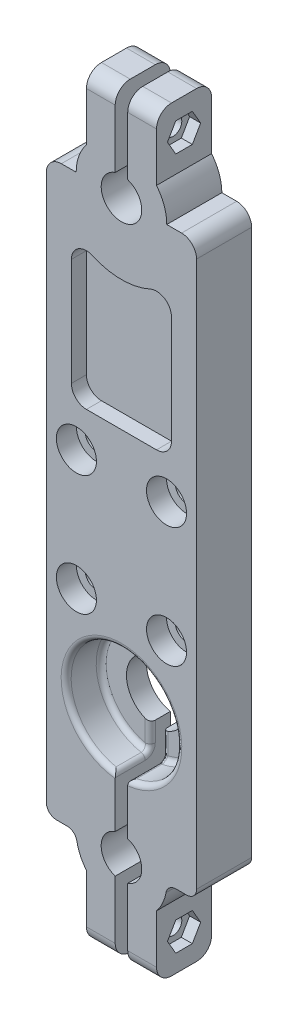
SolidWorks part; units mm, degrees
material "ABS"
ref_plane "Front Plane" through (0, 0, 0) normal (0, 0, 1) x (1, 0, 0)
ref_plane "Top Plane" through (0, 0, 0) normal (0, 1, 0) x (1, 0, 0)
ref_plane "Right Plane" through (0, 0, 0) normal (1, 0, 0) x (0, 0, -1)
sketch "Sketch2" plane through (0, 0, 0) normal (0, 0, 1) x (1, 0, 0)
  line L1 (-15, -17) -> (15, -17)
  line L2 (-15, -17) -> (-15, 17)
  line L3 (-15, 17) -> (15, 17)
  line L4 (15, -17) -> (15, 17)
  line L5 (-15, -17) -> (15, 17) construction
  line L6 (-15, 17) -> (15, -17) construction
  line L7 (-9, -12) -> (9, -12) construction
  line L8 (-9, -12) -> (-9, 12) construction
  line L9 (-9, 12) -> (9, 12) construction
  line L10 (9, -12) -> (9, 12) construction
  line L11 (-9, -12) -> (9, 12) construction
  line L12 (-9, 12) -> (9, -12) construction
  point P0 (0, 0)
  point P6 (0, 0)
  dimension "D1" = 34
  dimension "D2" = 30
  dimension "D3" = 5
  dimension "D4" = 6
extrude "Boss-Extrude1" add sketch "Sketch2" along normal blind 11 contours L3 L4 L1 L2
hole_wizard "CBORE for M4 SHCS1" positions "Sketch3" profile "Sketch4" counterbore size "M4" standard "ANSI Metric" end condition through all
sketch "Sketch3" plane through (0, 0, 11) normal (0, 0, 1) x (1, 0, 0)
  point P0 (-9, 12)
  point P3 (9, 12)
  point P6 (-9, -12)
  point P9 (9, -12)
sketch "Sketch4" plane through (-9, 12, 11) normal (1, 0, 0) x (0, -1, 0)
  line L0 (0, 0) -> (0, 11)
  line L1 (0, 11) -> (2.25, 11)
  line L3 (2.25, 11) -> (2.25, 4)
  line L4 (2.25, 4) -> (4, 4)
  line L5 (4, 4) -> (4, 0)
  line L7 (4, 0) -> (0, 0)
  line L11 (0, -6.35) -> (0, 107.95) construction
  dimension "Thru Hole Dia." = 4.5
  dimension "Thru Hole Depth" = 11
  dimension "C'Bore Dia." = 8
  dimension "C'Bore Depth" = 4
sketch "Sketch6" plane through (0, 0, 0) normal (0, 0, 1) x (1, 0, 0)
  line L0 (15, -17) -> (15, 17) construction
  line L1 (-15, -17) -> (15, -17)
  line L2 (-15, -17) -> (-15, -72.5)
  line L3 (-15, -72.5) -> (15, -72.5)
  line L4 (15, -17) -> (15, -72.5)
  line L5 (15, -17) -> (15, 17) construction
  line L6 (-15, 17) -> (15, 17)
  line L7 (-15, 17) -> (-15, 78.5)
  line L8 (-15, 78.5) -> (15, 78.5)
  line L9 (15, 17) -> (15, 78.5)
  circle A0 centre (0, -29) radius 11.05
  circle A1 centre (0, -54) radius 4.05
  circle A2 centre (0, -29) radius 10 construction
  circle A3 centre (0, -54) radius 4.05 construction
  circle A4 centre (0, 60) radius 4.05
  dimension "D1" = 22.1
  dimension "D3" = 8.1
  dimension "D5" = 18.5
  dimension "D2" = 60
  dimension "D4" = 55.5
extrude "Boss-Extrude2" add sketch "Sketch6" along normal up to surface (11 mm away) up to face at (-5, 12, 11)
sketch "Sketch8" plane through (0, 0, 0) normal (0, 0, 1) x (1, 0, 0)
  circle A0 centre (0, -29) radius 6
  circle A1 centre (0, -29) radius 11.05
  circle A2 centre (0, -29) radius 11.05 construction
  dimension "D1" = 12
extrude "Boss-Extrude3" add sketch "Sketch8" along normal blind 4 from surface starting at face at (-6.75, 12, 0)
sketch "Sketch7" plane through (0, 0, 11) normal (0, 0, 1) x (1, 0, 0)
  line L0 (-1.25, -72.5) -> (-1.25, 78.5)
  line L5 (-7, -59.7361) -> (-7, -72.5)
  line L6 (-1.25, -72.5) -> (1.25, -72.5)
  line L7 (7, -59.7361) -> (7, -72.5)
  line L8 (-1.25, 78.5) -> (1.25, 78.5)
  line L9 (-15, 78.5) -> (-15, -72.5)
  line L10 (-15, -72.5) -> (15, -72.5)
  line L11 (15, -72.5) -> (15, 78.5)
  line L12 (15, 78.5) -> (-15, 78.5)
  line L13 (-15, 78.5) -> (-15, -72.5)
  line L15 (15, -72.5) -> (15, 78.5)
  line L17 (-9.05, -54) -> (-15, -54)
  line L18 (9.05, -54) -> (15, -54)
  line L19 (1.25, -72.5) -> (1.25, 78.5)
  line L20 (-1.25, -72.5) -> (1.25, 78.5) construction
  line L21 (-7, -59.7361) -> (7, -59.7361) construction
  line L22 (-1.25, 78.5) -> (1.25, -72.5) construction
  line L26 (-15, -72.5) -> (15, -72.5)
  line L31 (-15, 60) -> (-9.05, 60)
  line L32 (9.05, 60) -> (15, 60)
  line L33 (-7, 78.5) -> (-7, 65.7361)
  line L34 (7, 78.5) -> (7, 65.7361)
  line L35 (15, 78.5) -> (-15, 78.5)
  circle A0 centre (0, -29) radius 11.05 construction
  circle A1 centre (0, -29) radius 11.05
  circle A4 centre (0, -54) radius 9.05
  circle A5 centre (0, -54) radius 9.05
  circle A8 centre (0, 60) radius 9.05
  point P1 (0, 3)
  line M9 (-15, 78.5) -> (-15, -72.5)
  line M10 (-15, -72.5) -> (15, -72.5)
  line M11 (15, -72.5) -> (15, 78.5)
  circle M13 centre (0, -54) radius 4.05
  circle M14 centre (0, -29) radius 11.05
  line M52 (15, 78.5) -> (-15, 78.5)
  circle M53 centre (0, 60) radius 4.05
  dimension "D3" = 14
  dimension "D4" = 2.5
  dimension "D1" = 0
  dimension "D2" = 5
extrude "Cut-Extrude1" cut sketch "Sketch7" against normal through all and the other way through all contours A5 L17 L13 L5 M10 | A5 L7 L18 M10 M11 | A5 L0 L19 M10 | L19 A5 L0 M13 | A5 L19 L0 M14 | L19 L0 M14 | L0 A5 L19 M13 | A8 L33 L31 M52 M9 | A8 L19 L0 M52 | A8 L32 L34 M11 M52 | L19 A8 L0 M53 region at (0, -67.7605, 11) region at (0, -60.5027, 11) region at (-11.1821, -63.6555, 11) region at (11.1821, -63.6555, 11) region at (0, -47.4973, 11) region at (0, -42.5026, 11) region at (-11.1821, 69.6555, 11) region at (0, -29, 11) region at (11.1821, 69.6555, 11) region at (0, 73.7605, 11) region at (0, 66.5027, 11)
fillet "Fillet2" radius 2 4 edges at (15, -54, 5.5) (-15, -54, 5.5) (-9.05, -54, 5.5) (9.05, -54, 5.5)
fillet "Fillet3" radius 1 12 edges at (0, -17.95, 0) (-1.25, -18.0209, 2) (-11.05, -29, 4) (-1.25, -39.9791, 7.5) (0, -17.95, 11) (1.25, -39.9791, 7.5) (11.05, -29, 4) (1.25, -18.0209, 2) (1.25, -37.4237, 4) (1.25, -20.5763, 0) (-1.25, -20.5763, 0) (-1.25, -37.4237, 4)
sketch "Sketch9" plane through (7, 0, 0) normal (1, 0, 0) x (0, 0, -1)
  line L0 (-11, -59.7361) -> (-11, -72.5) construction
  line L1 (-11, -72.5) -> (-11, -59.7361) construction
  line L2 (0, -72.5) -> (-11, -72.5) construction
  line L4 (-2.186, -66.118) -> (-3.843, -63.248)
  line L5 (-3.843, -63.248) -> (-7.157, -63.248)
  line L6 (-7.157, -63.248) -> (-8.814, -66.118)
  line L7 (-8.814, -66.118) -> (-7.157, -68.988)
  line L8 (-7.157, -68.988) -> (-3.843, -68.988)
  line L9 (-3.843, -68.988) -> (-2.186, -66.118)
  circle A0 centre (-5.5, -66.118) radius 1.75
  circle A1 centre (-5.5, -66.118) radius 2.87 construction
  point P7 (-11, -66.118)
  point P11 (-5.5, -72.5)
  dimension "D1" = 3.5
  dimension "D2" = 5.74
extrude "Cut-Extrude2" cut sketch "Sketch9" against normal through all contours A0
extrude "Cut-Extrude3" cut sketch "Sketch9<3>" against normal blind 2.2
sketch "Sketch9<3>" plane through (7, 0, 0) normal (1, 0, 0) x (0, 0, -1) same geometry as "Sketch9"
ref_plane "Plane1" through (0, 3, 0) normal (0, 1, 0) x (1, 0, 0)
mirror "Mirror1" about plane through (0, 3, 0) normal (0, 1, 0) of "Cut-Extrude3", "Cut-Extrude2"
fillet "Fillet4" radius 3 10 edges at (4.125, -72.5, 0) (4.125, -72.5, 11) (-4.125, -72.5, 11) (-4.125, -72.5, 0) (-4.125, 78.5, 11) (4.125, 78.5, 11) (4.125, 78.5, 0) (-4.125, 78.5, 0) (-15, 60, 5.5) (15, 60, 5.5)
ref_plane "Plane2" through (0, 0, 5.5) normal (0, 0, -1) x (-1, 0, 0)
sketch "Sketch11" plane through (0, 0, 0) normal (0, 0, 1) x (1, 0, 0)
  line L40 (-10, 50.1307) -> (-10, 20)
  line L41 (-10, 20) -> (10, 20)
  line L42 (10, 20) -> (10, 50.1307)
  line L43 (-15, -52) -> (-15, 57) construction
  arc A2 (-4.3364, 73.3641) -> (4.3364, 73.3641) centre (0, 60) ccw
  arc A3 (-4.3364, 73.3641) -> (4.3364, 73.3641) centre (0, 60) ccw
  point P2 (0, 20)
  dimension "D2" = 5
  dimension "D3" = 20
  dimension "D1" = 10
extrude "Cut-Extrude4" cut sketch "Sketch11" along normal blind 3 contours A3 L40 L41 L42 region at (0, 33.6511, 0)
mirror "Mirror2" about plane through (0, 0, 5.5) normal (0, 0, -1) of "Cut-Extrude4"
fillet "Fillet5" radius 3 8 edges at (-10, 50.1307, 9.5) (-10, 20, 9.5) (10, 20, 9.5) (10, 50.1307, 9.5) (10, 20, 1.5) (-10, 20, 1.5) (-10, 50.1307, 1.5) (10, 50.1307, 1.5)
